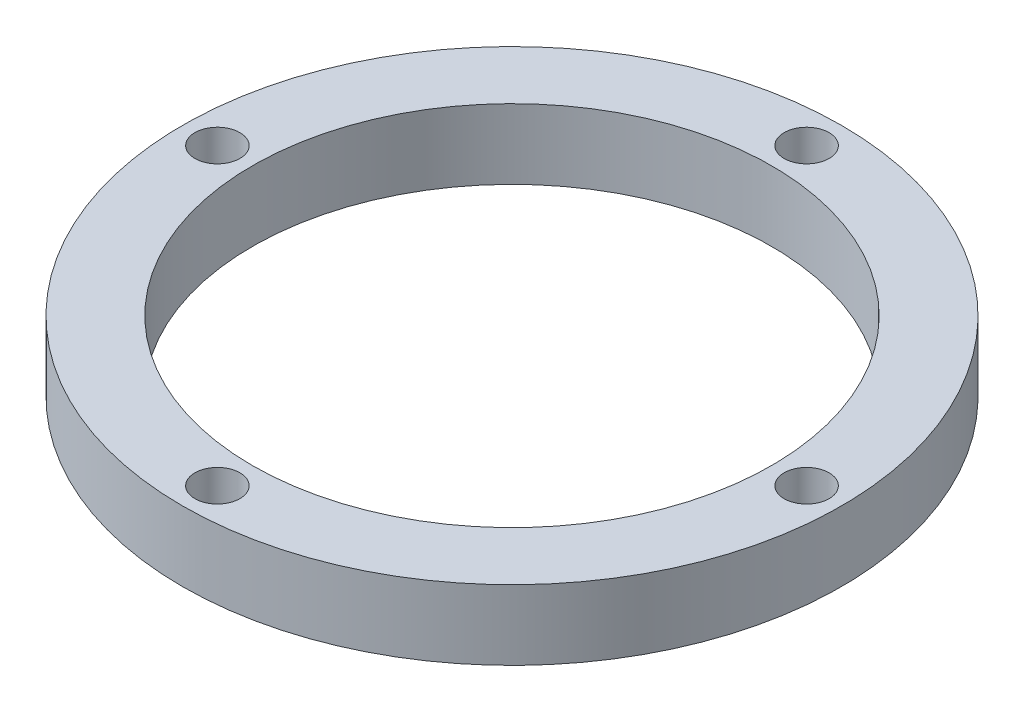
SolidWorks part; units mm, degrees
ref_plane "Front Plane" through (0, 0, 0) normal (0, 0, 1) x (1, 0, 0)
ref_plane "Top Plane" through (0, 0, 0) normal (0, 1, 0) x (1, 0, 0)
ref_plane "Right Plane" through (0, 0, 0) normal (1, 0, 0) x (0, 0, -1)
sketch "Sketch1" plane through (0, 0, 0) normal (0, 1, 0) x (1, 0, 0)
  circle A0 centre (0, 0) radius 26
  circle A1 centre (0, 0) radius 33
  dimension "D1" = 52
  dimension "D2" = 7
extrude "Boss-Extrude1" add sketch "Sketch1" along normal blind 7
sketch "Sketch5" plane through (0, 7, 0) normal (0, 1, 0) x (1, 0, 0)
  circle A0 centre (29.5, 0) radius 2.25
  circle A1 centre (0, 0) radius 26 construction
  dimension "D1" = 4.5
  dimension "D2" = 29.5
extrude "Cut-Extrude1" cut sketch "Sketch5" against normal through all
sketch "Sketch7" plane through (0, 0, 0) normal (0, 0, 1) x (1, 0, 0)
  line L0 (0, 0) -> (0, 5.0232) construction
pattern_circular "CirPattern1" count 4 over 360 about axis through (0, 0, 0) along (0, 1, 0) of "Cut-Extrude1" reverse direction yes
